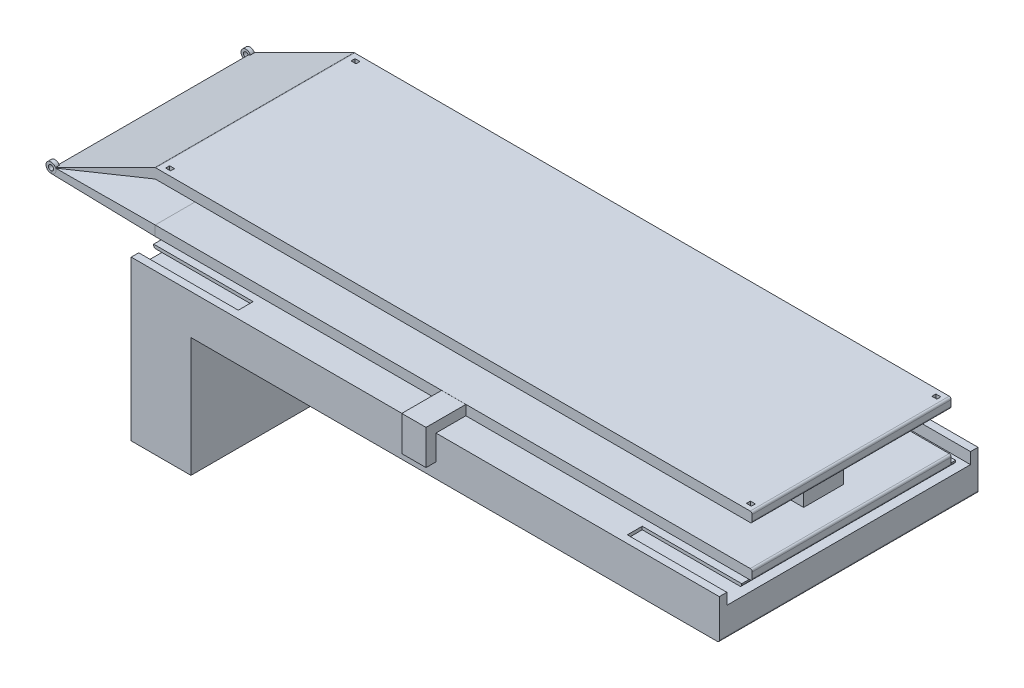
SolidWorks part; units mm, degrees
ref_plane "Front Plane" through (0, 0, 0) normal (0, 0, 1) x (1, 0, 0)
ref_plane "Top Plane" through (0, 0, 0) normal (0, 1, 0) x (1, 0, 0)
ref_plane "Right Plane" through (0, 0, 0) normal (1, 0, 0) x (0, 0, -1)
sketch "Sketch1" plane through (0, 0, 0) normal (0, 1, 0) x (1, 0, 0)
  line L1 (-381, 127) -> (381, 127)
  line L2 (-381, 127) -> (-381, -127)
  line L3 (-381, -127) -> (381, -127)
  line L4 (381, 127) -> (381, -127)
  line L5 (-381, 127) -> (381, -127) construction
  line L6 (-381, -127) -> (381, 127) construction
  point P1 (0, 0)
extrude "Boss-Extrude1" add sketch "Sketch1" along normal blind 12.7
sketch "Sketch2" plane through (0, 0, 127) normal (0, 0, 1) x (1, 0, 0)
  line L0 (-381, 12.7) -> (-514.0567, -53.9116)
  line L1 (-514.0567, -53.9116) -> (-381, 0)
  line L2 (-381, 0) -> (-381, 12.7)
  point P3 (-473.6028, -55.2749)
  point P6 (-498.5009, -44.7612)
  point P7 (-514.0567, -53.9116)
extrude "Boss-Extrude2" add sketch "Sketch2" against normal up to vertex (254 mm away) up to point (-381, 12.7, -127)
sketch "Sketch5" plane through (0, 0, 127) normal (0, 0, 1) x (1, 0, 0)
  circle A0 centre (-514.0567, -53.9116) radius 3.302
  circle A1 centre (-514.0567, -53.9116) radius 6.35
sketch "Sketch9" plane through (0, 12.7, 0) normal (0, 1, 0) x (1, 0, 0)
  line L0 (-15.4208, 0) -> (15.4208, 0) construction
  line L1 (367.4986, -115.8342) -> (373.8486, -115.8342)
  line L2 (367.4986, -115.8342) -> (367.4986, -120.9142)
  line L3 (367.4986, -120.9142) -> (373.8486, -120.9142)
  line L4 (373.8486, -115.8342) -> (373.8486, -120.9142)
  line L5 (367.4986, -115.8342) -> (373.8486, -120.9142) construction
  line L6 (367.4986, -120.9142) -> (373.8486, -115.8342) construction
  line L7 (367.4986, 120.9142) -> (373.8486, 115.8342) construction
  line L8 (367.4986, 115.8342) -> (373.8486, 120.9142) construction
  line L9 (373.8486, 115.8342) -> (373.8486, 120.9142)
  line L10 (367.4986, 120.9142) -> (373.8486, 120.9142)
  line L11 (367.4986, 115.8342) -> (367.4986, 120.9142)
  line L12 (367.4986, 115.8342) -> (373.8486, 115.8342)
  line L13 (0, -15.4208) -> (0, 15.4208) construction
  line L14 (-367.4986, 115.8342) -> (-373.8486, 120.9142) construction
  line L15 (-367.4986, 120.9142) -> (-373.8486, 115.8342) construction
  line L16 (-367.4986, 115.8342) -> (-373.8486, 115.8342)
  line L17 (-367.4986, 115.8342) -> (-367.4986, 120.9142)
  line L18 (-367.4986, 120.9142) -> (-373.8486, 120.9142)
  line L19 (-373.8486, 115.8342) -> (-373.8486, 120.9142)
  line L20 (-367.4986, -120.9142) -> (-373.8486, -115.8342) construction
  line L21 (-367.4986, -115.8342) -> (-373.8486, -120.9142) construction
  line L22 (-373.8486, -115.8342) -> (-373.8486, -120.9142)
  line L23 (-367.4986, -120.9142) -> (-373.8486, -120.9142)
  line L24 (-367.4986, -115.8342) -> (-367.4986, -120.9142)
  line L25 (-367.4986, -115.8342) -> (-373.8486, -115.8342)
  point P0 (370.6736, -118.3742)
  point P12 (370.6736, 118.3742)
  point P20 (-370.6736, 118.3742)
  point P25 (-370.6736, -118.3742)
extrude "Cut-Extrude1" cut sketch "Sketch9" against normal through all
sketch "Sketch10" plane through (0, 0, 127) normal (0, 0, 1) x (1, 0, 0)
extrude "Boss-Extrude8" add sketch "Sketch5" against normal blind 5.08
sketch "Sketch13" plane through (0, 0, 0) normal (0, -1, 0) x (1, 0, 0)
  line L0 (41.91, 0) -> (-41.91, 0) construction
  line L1 (238.3726, 25.4) -> (339.9726, 25.4)
  line L2 (238.3726, 25.4) -> (238.3726, -25.4)
  line L3 (238.3726, -25.4) -> (339.9726, -25.4)
  line L4 (339.9726, 25.4) -> (339.9726, -25.4)
  line L5 (238.3726, 25.4) -> (339.9726, -25.4) construction
  line L6 (238.3726, -25.4) -> (339.9726, 25.4) construction
  point P0 (289.1726, 0)
extrude "Boss-Extrude10" add sketch "Sketch13" along normal blind 50.8
sketch "Sketch15" plane through (339.9726, 0, 0) normal (1, 0, 0) x (0, 0, -1)
  line L0 (0, 6.985) -> (0, -6.985) construction
  circle A0 centre (0, -25.4217) radius 20.32
extrude "Cut-Extrude3" cut sketch "Sketch15" against normal blind 90.17
sketch "Sketch16" plane through (339.9726, 0, 0) normal (1, 0, 0) x (0, 0, -1)
  line L0 (139.7, 0) -> (-139.7, 0) construction
  line L1 (-25.4, 0) -> (25.4, 0)
  line L2 (-25.4, 0) -> (-25.4, -50.8)
  line L3 (-25.4, -50.8) -> (25.4, -50.8)
  line L4 (25.4, 0) -> (25.4, -50.8)
  line L5 (-25.4, -50.8) -> (-25.4, 0) construction
extrude "Boss-Extrude11" add sketch "Sketch16" along normal blind 5.08
sketch "Sketch17" plane through (345.0526, 0, 0) normal (1, 0, 0) x (0, 0, -1)
  line L0 (-25.4, 0) -> (25.4, -50.8) construction
  line L1 (139.7, 0) -> (-139.7, 0) construction
  line L2 (-25.4, 0) -> (-25.4, -50.8) construction
  line L3 (25.4, -50.8) -> (25.4, 0) construction
  line L4 (-25.4, -50.8) -> (25.4, -50.8) construction
  line L5 (-25.4, -50.8) -> (25.4, 0) construction
  circle A0 centre (0, -25.4) radius 5.334
extrude "Cut-Extrude4" cut sketch "Sketch17" against normal up to next
sketch "Sketch19" plane through (238.3726, 0, 0) normal (-1, 0, 0) x (0, 0, 1)
  line L0 (0, -6.985) -> (0, 6.985) construction
  line L1 (-6.35, -6.7163) -> (6.35, -6.7163)
  line L2 (-6.35, -6.7163) -> (-6.35, -19.4163)
  line L3 (-6.35, -19.4163) -> (6.35, -19.4163)
  line L4 (6.35, -6.7163) -> (6.35, -19.4163)
  line L5 (-6.35, -6.7163) -> (6.35, -19.4163) construction
  line L6 (-6.35, -19.4163) -> (6.35, -6.7163) construction
  point P0 (0, -13.0663)
extrude "Cut-Extrude6" cut sketch "Sketch19" against normal up to next
sketch "Sketch20" plane through (0, -50.8, 0) normal (0, -1, 0) x (1, 0, 0)
  line L1 (-381, 127) -> (381, 127)
  line L2 (-381, 127) -> (-381, -127)
  line L3 (-381, -127) -> (381, -127)
  line L4 (381, 127) -> (381, -127)
  line L5 (-381, 127) -> (381, -127) construction
  line L6 (-381, -127) -> (381, 127) construction
  point P0 (0, 0)
extrude "Boss-Extrude12" add sketch "Sketch20" along normal blind 12.7
sketch "Sketch12" plane through (0, 0, -127) normal (0, 0, -1) x (-1, 0, 0)
  circle A0 centre (514.0567, -53.9116) radius 3.302
  circle A1 centre (514.0567, -53.9116) radius 6.35
mirror "Mirror1" about plane through (0, 0, 0) normal (0, 0, 1) of "Boss-Extrude8"
sketch "Sketch22" plane through (0, 0, 127) normal (0, 0, 1) x (1, 0, 0)
  line L2 (-381, -63.5) -> (-381, -50.8)
  line L3 (-514.0567, -53.9116) -> (-514.0567, -60.2616)
  line L4 (-514.0567, -60.2616) -> (-381, -63.5)
  line L5 (-381, -50.8) -> (-508.1714, -51.5271)
  line L6 (-508.1714, -51.5271) -> (-514.0567, -53.9116)
  arc A0 (-508.3785, -51.069) -> (-508.1714, -51.5271) centre (-514.0567, -53.9116) ccw construction
extrude "Boss-Extrude15" add sketch "Sketch22" against normal up to vertex (254 mm away) separate body up to point (-514.0567, -53.9116, -127)
sketch "Sketch23" plane through (0, 0, 127) normal (0, 0, 1) x (1, 0, 0)
  circle A0 centre (-514.0567, -53.9116) radius 3.302
extrude "Cut-Extrude7" cut sketch "Sketch23" against normal through all
sketch "Sketch24" plane through (0, -63.5, 0) normal (0, -1, 0) x (1, 0, 0)
  line L0 (41.91, 0) -> (-41.91, 0) construction
  line L1 (-373.4876, 165.1) -> (377.1051, 165.1)
  line L2 (-373.4876, 165.1) -> (-373.4876, -165.1)
  line L3 (-373.4876, -165.1) -> (377.1051, -165.1)
  line L4 (377.1051, 165.1) -> (377.1051, -165.1)
  line L5 (-373.4876, 165.1) -> (377.1051, -165.1) construction
  line L6 (-373.4876, -165.1) -> (377.1051, 165.1) construction
  point P0 (1.8088, 0)
extrude "Boss-Extrude16" add sketch "Sketch24" along normal blind 50.8
sketch "Sketch28" plane through (0, -114.3, 0) normal (0, -1, 0) x (1, 0, 0)
  line L0 (-373.4876, -165.1) -> (377.1051, -165.1) construction
  line L1 (-373.4876, 165.1) -> (-297.2876, 165.1)
  line L2 (-373.4876, 165.1) -> (-373.4876, -165.1)
  line L3 (-373.4876, -165.1) -> (-297.2876, -165.1)
  line L4 (-297.2876, 165.1) -> (-297.2876, -165.1)
extrude "Boss-Extrude17" add sketch "Sketch28" along normal blind 152.4
extrude "Boss-Extrude9" add sketch "Sketch12" against normal blind 5.08
sketch "Sketch29" plane through (238.3726, 0, 0) normal (-1, 0, 0) x (0, 0, 1)
  line L0 (0, -69.85) -> (0, 69.85) construction
  line L1 (-12.7, -0.4389) -> (12.7, -0.4389)
  line L2 (-12.7, -0.4389) -> (-12.7, -25.8389)
  line L3 (-12.7, -25.8389) -> (12.7, -25.8389)
  line L4 (12.7, -0.4389) -> (12.7, -25.8389)
  line L5 (-12.7, -0.4389) -> (12.7, -25.8389) construction
  line L6 (-12.7, -25.8389) -> (12.7, -0.4389) construction
  point P0 (0, -13.1389)
extrude "Boss-Extrude18" add sketch "Sketch29" along normal blind 50.8
sketch "Sketch30" plane through (0, -50.8, 0) normal (0, 1, 0) x (1, 0, 0)
  line L0 (-69.85, 0) -> (69.85, 0) construction
  line L1 (180.5558, 12.7) -> (205.9558, 12.7)
  line L2 (180.5558, 12.7) -> (180.5558, -12.7)
  line L3 (180.5558, -12.7) -> (205.9558, -12.7)
  line L4 (205.9558, 12.7) -> (205.9558, -12.7)
  line L5 (180.5558, 12.7) -> (205.9558, -12.7) construction
  line L6 (180.5558, -12.7) -> (205.9558, 12.7) construction
  point P0 (193.2558, 0)
extrude "Boss-Extrude19" add sketch "Sketch30" along normal up to surface (50.8 mm away) up to face at (-370.6736, 0, 118.3742)
sketch "Sketch31" plane through (0, 0, 127) normal (0, 0, 1) x (1, 0, 0)
  line L0 (0, -69.85) -> (0, 69.85) construction
  line L1 (-15.4635, -50.8958) -> (15.4635, -50.8958)
  line L2 (-15.4635, -50.8958) -> (-15.4635, -95.3747)
  line L3 (-15.4635, -95.3747) -> (15.4635, -95.3747)
  line L4 (15.4635, -50.8958) -> (15.4635, -95.3747)
  line L5 (-15.4635, -50.8958) -> (15.4635, -95.3747) construction
  line L6 (-15.4635, -95.3747) -> (15.4635, -50.8958) construction
  point P0 (0, -73.1353)
extrude "Boss-Extrude20" add sketch "Sketch31" along normal blind 50.8
sketch "Sketch25" plane through (-373.4876, 0, 0) normal (-1, 0, 0) x (0, 0, 1)
  line L0 (0, -41.91) -> (0, 41.91) construction
  line L1 (-155.5171, -67.4497) -> (155.5171, -67.4497)
  line L2 (-155.5171, -67.4497) -> (-155.5171, -77.9143)
  line L3 (-155.5171, -77.9143) -> (155.5171, -77.9143)
  line L4 (155.5171, -67.4497) -> (155.5171, -77.9143)
  line L5 (-155.5171, -67.4497) -> (155.5171, -77.9143) construction
  line L6 (-155.5171, -77.9143) -> (155.5171, -67.4497) construction
  point P0 (0, -72.682)
extrude "Cut-Extrude8" cut sketch "Sketch25" against normal through all
sketch "Sketch32" plane through (-373.4876, 0, 0) normal (-1, 0, 0) x (0, 0, 1)
  line L1 (155.5171, -67.4497) -> (136.4671, -67.4497)
  line L2 (155.5171, -67.4497) -> (155.5171, -53.2082)
  line L3 (155.5171, -53.2082) -> (136.4671, -53.2082)
  line L4 (136.4671, -67.4497) -> (136.4671, -53.2082)
  line L5 (-155.5171, -67.4497) -> (-136.4671, -67.4497)
  line L6 (-155.5171, -67.4497) -> (-155.5171, -53.2082)
  line L7 (-155.5171, -53.2082) -> (-136.4671, -53.2082)
  line L8 (-136.4671, -67.4497) -> (-136.4671, -53.2082)
extrude "Cut-Extrude9" cut sketch "Sketch32" against normal blind 127
sketch "Sketch33" plane through (377.1051, 0, 0) normal (1, 0, 0) x (0, 0, -1)
  line L1 (-155.5171, -67.4497) -> (-136.4671, -67.4497)
  line L2 (-155.5171, -67.4497) -> (-155.5171, -43.8313)
  line L3 (-155.5171, -43.8313) -> (-136.4671, -43.8313)
  line L4 (-136.4671, -67.4497) -> (-136.4671, -43.8313)
  line L5 (155.5171, -67.4497) -> (136.4671, -67.4497)
  line L6 (155.5171, -67.4497) -> (155.5171, -53.2082)
  line L7 (155.5171, -53.2082) -> (136.4671, -53.2082)
  line L8 (136.4671, -67.4497) -> (136.4671, -53.2082)
extrude "Cut-Extrude10" cut sketch "Sketch33" against normal blind 127
fillet "Fillet1" radius 2.54 8 edges at (-373.4876, -67.4497, 0) (377.1051, -114.3, 0) (381, 0, 0) (381, -50.8, 0) (381, -63.5, 0) (377.1051, -67.4497, 0) (381, 12.7, 0) (-381, 12.7, 0)
